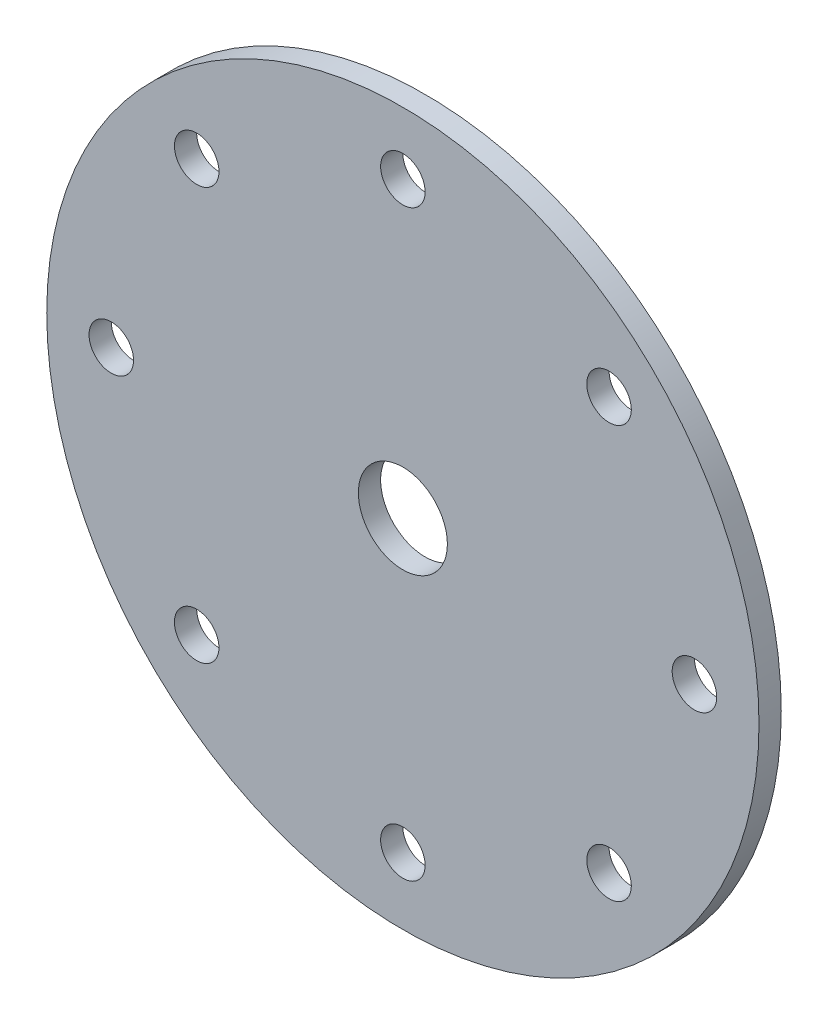
SolidWorks part; units mm, degrees
material "Plain Carbon Steel"
ref_plane "Front Plane" through (0, 0, 0) normal (0, 0, 1) x (1, 0, 0)
ref_plane "Top Plane" through (0, 0, 0) normal (0, 1, 0) x (1, 0, 0)
ref_plane "Right Plane" through (0, 0, 0) normal (1, 0, 0) x (0, 0, -1)
sketch "Sketch1" plane through (0, 0, 0) normal (0, 0, 1) x (1, 0, 0)
  line L0 (0, 101.6) -> (0, -101.6) construction
  line L1 (-101.6, 0) -> (101.6, 0) construction
  line L2 (-58.8207, 59.4557) -> (58.8207, -58.1857) construction
  line L3 (-58.8207, -58.1857) -> (58.8207, 59.4557) construction
  circle A0 centre (0, 0) radius 101.6
  circle A1 centre (0, 0) radius 12.7
  circle A2 centre (0, 83.82) radius 6.35
  circle A6 centre (58.8207, 59.4557) radius 6.35
  circle A7 centre (83.185, 0.635) radius 6.35
  circle A8 centre (58.8207, -58.1857) radius 6.35
  circle A9 centre (0, -82.55) radius 6.35
  circle A10 centre (-58.8207, -58.1857) radius 6.35
  circle A11 centre (-83.185, 0.635) radius 6.35
  circle A12 centre (-58.8207, 59.4557) radius 6.35
  dimension "D1" = 203.2
  dimension "D2" = 25.4
  dimension "D3" = 12.7
  dimension "D6" = 19.05
  dimension "D4" = 17.78
  dimension "D5" = 8
extrude "Rotor Disc" add sketch "Sketch1" along normal blind 6.35 contours A0 A12 A11 A10 A8 A7 A6 A1 A2 region at (-98.7263, 0, 0)
